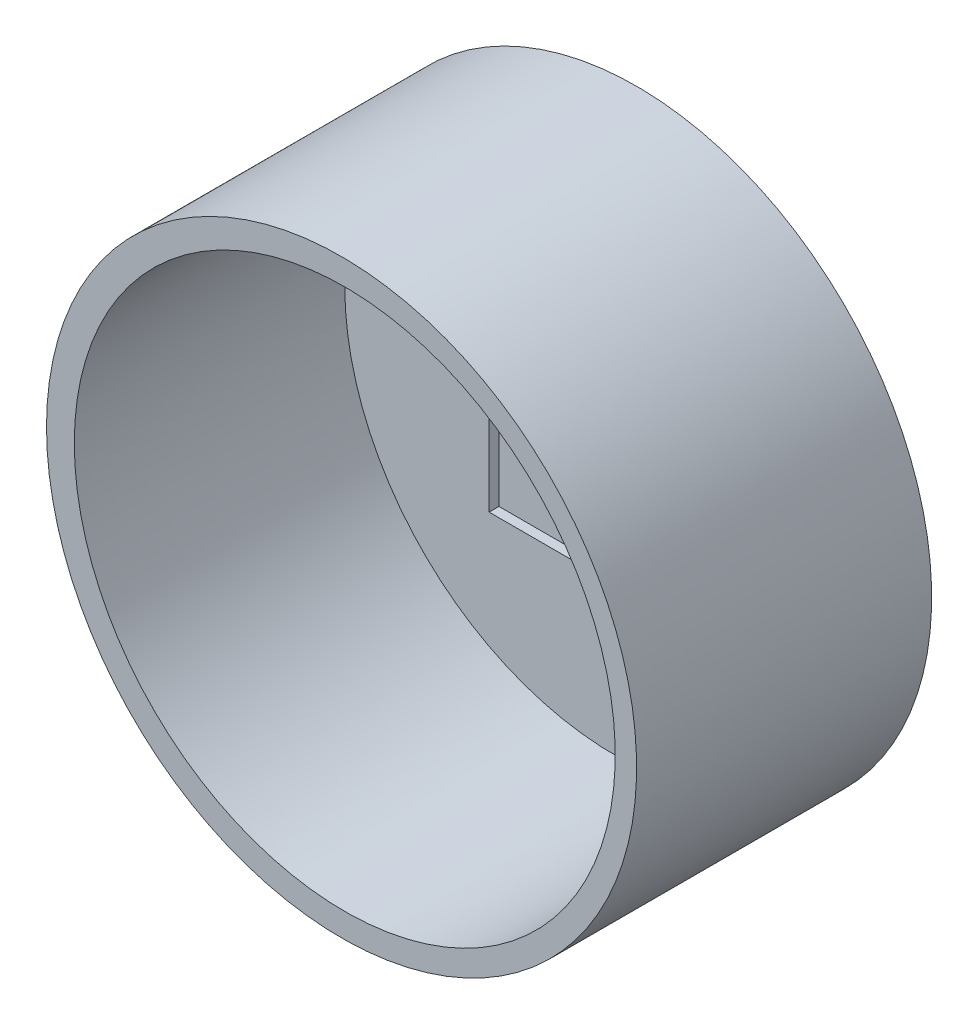
SolidWorks part; units mm, degrees
material "6061 Alloy"
ref_plane "Front Plane" through (0, 0, 0) normal (0, 0, 1) x (1, 0, 0)
ref_plane "Top Plane" through (0, 0, 0) normal (0, 1, 0) x (1, 0, 0)
ref_plane "Right Plane" through (0, 0, 0) normal (1, 0, 0) x (0, 0, -1)
sketch "Sketch1" plane through (0, 0, 0) normal (0, 0, 1) x (1, 0, 0)
  circle A0 centre (0, 0) radius 76.2
  circle A1 centre (0.8288, 0) radius 69.85
  dimension "D1" = 152.4
  dimension "D2" = 139.7
extrude "Boss-Extrude1" add sketch "Sketch1" along normal blind 76.2
sketch "Sketch3" plane through (0, 0, 0) normal (0, 0, 1) x (1, 0, 0)
  circle A0 centre (0, 0) radius 76.2
extrude "Boss-Extrude2" add sketch "Sketch3" along normal blind 6.35
sketch "Sketch4" plane through (0, 0, 6.35) normal (0, 0, 1) x (1, 0, 0)
  line L1 (-31.75, 31.75) -> (31.75, 31.75)
  line L2 (-31.75, 31.75) -> (-31.75, -31.75)
  line L3 (-31.75, -31.75) -> (31.75, -31.75)
  line L4 (31.75, 31.75) -> (31.75, -31.75)
  point P5 (0, 31.75)
  point P7 (-31.75, 0)
  dimension "D1" = 63.5
  dimension "2.5" = 63.5
extrude "Cut-Extrude1" cut sketch "Sketch4" against normal blind 2.54
